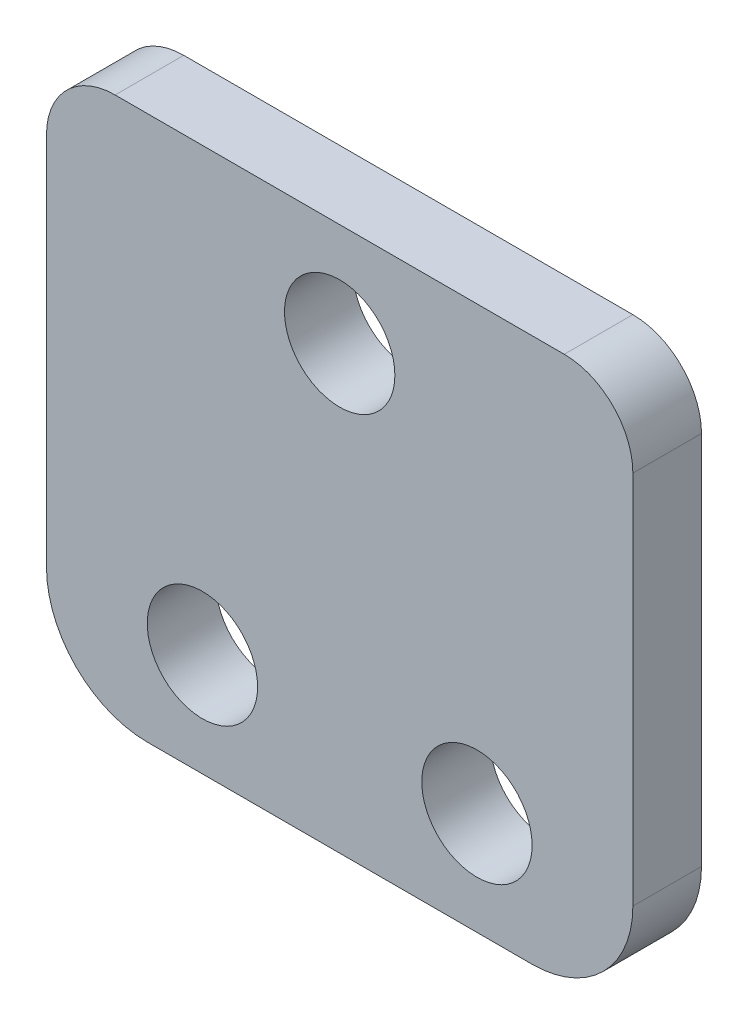
SolidWorks part; units mm, degrees
ref_plane "Front Plane" through (0, 0, 0) normal (0, 0, 1) x (1, 0, 0)
ref_plane "Top Plane" through (0, 0, 0) normal (0, 1, 0) x (1, 0, 0)
ref_plane "Right Plane" through (0, 0, 0) normal (1, 0, 0) x (0, 0, -1)
sketch "Sketch1" plane through (0, 0, 0) normal (0, 0, 1) x (1, 0, 0)
  line L0 (8.9027, 4.6609) -> (-8.9027, 4.6609) construction
  line L1 (8.9027, 4.6609) -> (-8.9027, 4.6609)
  line L3 (10.3886, -4.6609) -> (-10.3886, -4.6609)
  line L4 (8.9027, 4.6609) -> (-8.9027, 4.6609)
  line L5 (-8.9027, -4.6609) -> (8.9027, -4.6609)
  line L6 (8.9027, 4.6609) -> (-8.9027, 4.6609)
  line L7 (-8.9027, -4.6609) -> (8.9027, -4.6609)
  line L8 (13.5636, -1.4859) -> (13.5636, 17.3482)
  line L9 (10.3886, 20.5232) -> (-10.3886, 20.5232)
  line L10 (-13.5636, -1.4859) -> (-13.5636, 17.3482)
  line L11 (-24.8301, 20.5232) -> (-69.2801, 20.5232) construction
  arc A0 (13.5636, 17.3482) -> (10.3886, 20.5232) centre (10.3886, 17.3482) ccw
  arc A1 (-10.3886, 20.5232) -> (-13.5636, 17.3482) centre (-10.3886, 17.3482) ccw
  arc A2 (8.9027, -4.6609) -> (8.9027, 4.6609) centre (8.9027, 0) ccw
  arc A3 (-8.9027, 4.6609) -> (-8.9027, -4.6609) centre (-8.9027, 0) ccw
  arc A4 (8.9027, -4.6609) -> (8.9027, 4.6609) centre (8.9027, 0) ccw
  arc A5 (-8.9027, 4.6609) -> (-8.9027, -4.6609) centre (-8.9027, 0) ccw
  arc A6 (-10.3886, -4.6609) -> (-13.5636, -1.4859) centre (-10.3886, -1.4859) cw
  arc A7 (10.3886, -4.6609) -> (13.5636, -1.4859) centre (10.3886, -1.4859) ccw
  dimension "D2" = 3.175
  dimension "D1" = 0
extrude "Boss-Extrude1" add sketch "Sketch1" along normal blind 3.175 contours A5 L1 A4 L8 A0 L9 A1 L10 | L1 A5 L3 A4 region at (0, 0, 0) region at (0, 12.3281, 0)
hole_wizard "#10 Clearance Hole1" positions "Sketch2" profile "Sketch3" hole size "#10" standard "ANSI Inch" end condition through all
sketch "Sketch2" plane through (0, 0, 3.175) normal (0, 0, 1) x (1, 0, 0)
  line L0 (0, -4.6609) -> (0, 20.5232) construction
  line L1 (8.9027, -4.6609) -> (-8.9027, -4.6609) construction
  line L2 (10.3886, 20.5232) -> (-10.3886, 20.5232) construction
  line L4 (6.35, 0.1016) -> (-6.35, 0.1016) construction
  point P0 (6.35, 0.1016)
  point P2 (-6.35, 0.1016)
  point P4 (0, 15.7607)
  point P21 (0, 0.1016)
  dimension "D1" = 12.7
  dimension "D2" = 4.7625
  dimension "D3" = 4.7625
sketch "Sketch3" plane through (6.35, 0.1016, 3.175) normal (1, 0, 0) x (0, -1, 0)
  line L0 (0, 0) -> (0, 3.175)
  line L1 (0, 3.175) -> (2.5527, 3.175)
  line L2 (2.5527, 3.175) -> (2.5527, 0)
  line L5 (2.5527, 0) -> (0, 0)
  line L11 (0, -6.35) -> (0, 107.95) construction
  dimension "Thru Hole Dia." = 5.1054
  dimension "Thru Hole Depth" = 3.175
